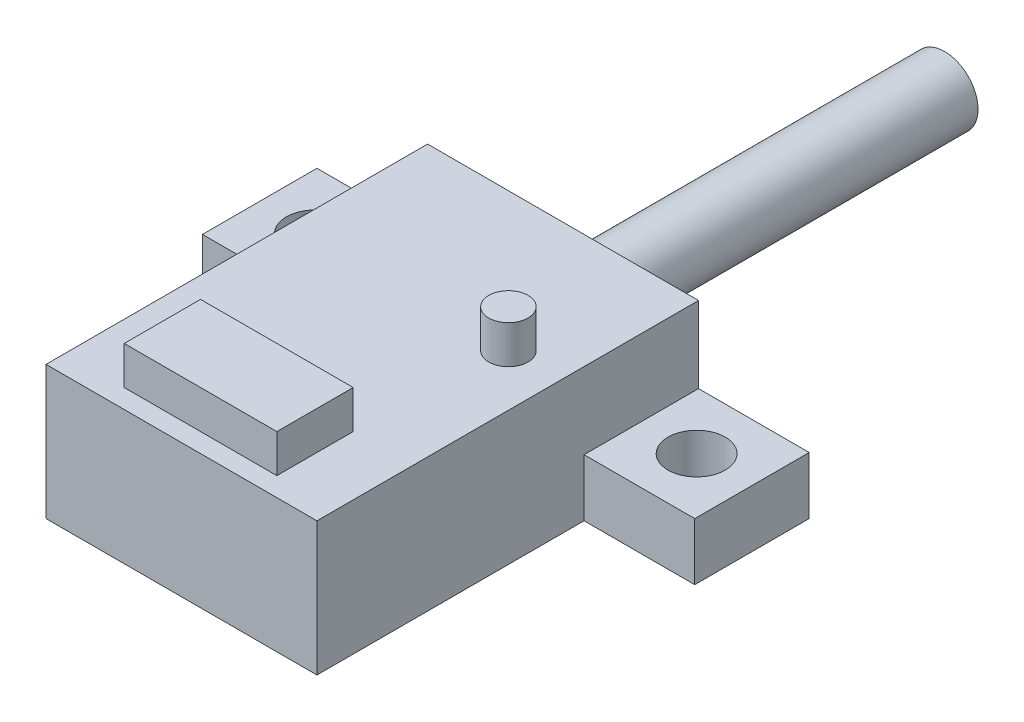
SolidWorks part; units mm, degrees
ref_plane "前视基准面" through (0, 0, 0) normal (0, 0, 1) x (1, 0, 0)
ref_plane "上视基准面" through (0, 0, 0) normal (0, 1, 0) x (1, 0, 0)
ref_plane "右视基准面" through (0, 0, 0) normal (1, 0, 0) x (0, 0, -1)
other "Configuration Table"
sketch "草图1" plane through (0, 0, 0) normal (0, 1, 0) x (1, 0, 0)
  line L0 (0, 0) -> (0, -50000) construction
  line L1 (-7.1, 10) -> (7.1, 10)
  line L2 (-7.1, 10) -> (-7.1, -10)
  line L3 (-7.1, -10) -> (7.1, -10)
  line L4 (7.1, 10) -> (7.1, -10)
  line L5 (-7.1, 10) -> (7.1, -10) construction
  line L6 (-7.1, -10) -> (7.1, 10) construction
  line L7 (0, 0) -> (50000, 0) construction
  line L8 (-12.9, 10) -> (-7.1, 4) construction
  line L9 (-7.1, 10) -> (-12.9, 10)
  line L10 (-7.1, 10) -> (-7.1, 4)
  line L11 (-7.1, 4) -> (-12.9, 4)
  line L12 (-12.9, 10) -> (-12.9, 4)
  line L13 (-7.1, 10) -> (-12.9, 4) construction
  line L14 (7.1, 4) -> (12.9, 4)
  line L15 (12.9, 10) -> (12.9, 4)
  line L16 (7.1, 10) -> (12.9, 10)
  line L17 (7.1, 10) -> (7.1, 4)
  circle A0 centre (-10, 7) radius 1.5
  circle A1 centre (10, 7) radius 1.5
  point P0 (0, 0)
  point P16 (0, 0)
  point P17 (-10, 7)
  dimension "D5" = 3
  dimension "D1" = 14.2
  dimension "D2" = 20
  dimension "D3" = 6
  dimension "D4" = 5.8
extrude "凸台-拉伸1" add sketch "草图1" along normal blind 7 contours L4 L1 L2 L3 region at (0, 0, 0)
extrude "凸台-拉伸2" add sketch "草图1<3>" along normal blind 3 contours L9 L12 L11 L2 A0 | L16 L4 L14 L15 A1 region at (-7.1835, 0, -7) region at (10, 0, -9.9165)
sketch "草图1<3>" plane through (0, 0, 0) normal (0, 1, 0) x (1, 0, 0) same geometry as "草图1"
sketch "草图2" plane through (0, 7, 0) normal (0, 1, 0) x (1, 0, 0)
  line L0 (0, 0) -> (0, -19.7625) construction
  line L1 (-4, -5) -> (4, -5)
  line L2 (-4, -5) -> (-4, -9)
  line L3 (-4, -9) -> (4, -9)
  line L4 (4, -5) -> (4, -9)
  line L5 (-10, 7) -> (10, 7) construction
  point P7 (4, -7)
  dimension "D1" = 8
  dimension "D2" = 4
  dimension "D3" = 14
extrude "凸台-拉伸3" add sketch "草图2" along normal blind 2
sketch "草图3" plane through (0, 7, 0) normal (0, 1, 0) x (1, 0, 0)
  line L0 (0, -10) -> (0, 10) construction
  line L1 (-7.1, -10) -> (7.1, -10) construction
  line L2 (-7.1, 10) -> (7.1, 10) construction
  circle A0 centre (4.3984, 2.7361) radius 1.0288
  point P8 (4.3984, 2.7361)
extrude "凸台-拉伸4" add sketch "草图3" along normal blind 2
sketch "草图4" plane through (0, 0, -10) normal (0, 0, -1) x (-1, 0, 0)
  line L0 (0, 0) -> (0, -50000) construction
  line L1 (12.9, 0) -> (-12.9, 0) construction
  line L2 (-13, 3) -> (49987, 3) construction
  circle A0 centre (0, 3) radius 1.75
  point P4 (0, 0)
  dimension "D1" = 3.5
extrude "凸台-拉伸5" add sketch "草图4" along normal blind 20
